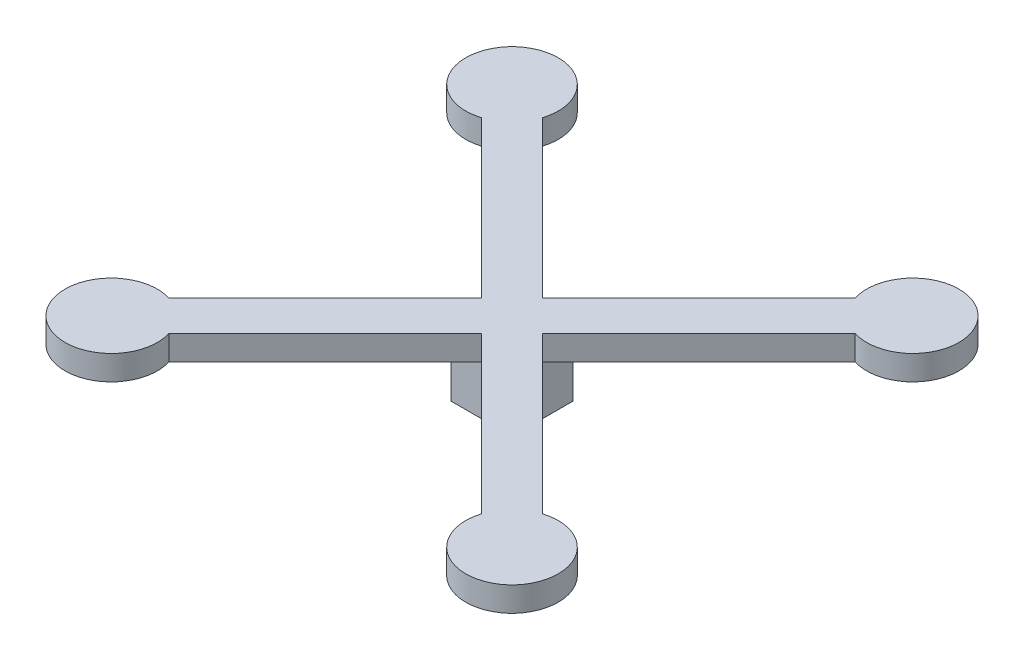
SolidWorks part; units mm, degrees
ref_plane "Front Plane" through (0, 0, 0) normal (0, 0, 1) x (1, 0, 0)
ref_plane "Top Plane" through (0, 0, 0) normal (0, 1, 0) x (1, 0, 0)
ref_plane "Right Plane" through (0, 0, 0) normal (1, 0, 0) x (0, 0, -1)
sketch "Sketch1" plane through (0, 0, 0) normal (0, 1, 0) x (1, 0, 0)
  line L0 (-12.3744, 12.3744) -> (12.3744, -12.3744)
  line L1 (12.3744, -12.3744) -> (175.0089, 150.2602)
  line L2 (175.0089, 150.2602) -> (150.2602, 175.0089)
  line L3 (150.2602, 175.0089) -> (-12.3744, 12.3744)
  line L4 (0, 0) -> (-70.3293, 0) construction
  line L5 (175.0089, -150.2602) -> (12.3744, 12.3744)
  line L6 (12.3744, 12.3744) -> (-12.3744, -12.3744)
  line L7 (-12.3744, -12.3744) -> (150.2602, -175.0089)
  line L8 (150.2602, -175.0089) -> (175.0089, -150.2602)
  line L9 (-150.2602, -175.0089) -> (12.3744, -12.3744)
  line L10 (12.3744, -12.3744) -> (-12.3744, 12.3744)
  line L11 (-12.3744, 12.3744) -> (-175.0089, -150.2602)
  line L12 (-175.0089, -150.2602) -> (-150.2602, -175.0089)
  line L13 (-175.0089, 150.2602) -> (-12.3744, -12.3744)
  line L14 (-12.3744, -12.3744) -> (12.3744, 12.3744)
  line L15 (12.3744, 12.3744) -> (-150.2602, 175.0089)
  line L16 (-150.2602, 175.0089) -> (-175.0089, 150.2602)
  circle A0 centre (162.6346, 162.6346) radius 37.5
  circle A1 centre (162.6346, -162.6346) radius 37.5
  circle A2 centre (-162.6346, -162.6346) radius 37.5
  circle A3 centre (-162.6346, 162.6346) radius 37.5
  point P4 (0, 0)
  point P31 (0, 0)
  dimension "D2" = 35
  dimension "D3" = 75
  dimension "D1" = 230
  dimension "D4" = 45
  dimension "D5" = 4
extrude "Boss-Extrude1" add sketch "Sketch1" along normal blind 20 contours L11 A2 L9 L12 | L9 A2 L11 L12 | A2 L9 L7 L13 L11 | L15 A3 L13 L16 | L13 A3 L15 L16 | A3 L13 L11 L3 L15 | A0 L3 L15 L5 L1 | L3 A0 L1 L2 | L1 A0 L3 L2 | A1 L5 L1 L9 L7 | L5 A1 L7 L8 | L7 A1 L5 L8 | L5 L6 L0 L1 | L7 L9 L0 L6 | L4 L0 L11 | L6 L15 L3 L0 | L6 L4 L13 region at (0, 0, -12.3744) region at (-74.7478, 0, -74.7478) region at (-12.3744, 0, -4.1248) region at (12.3744, 0, 0) region at (-12.3744, 0, 4.1248) region at (0, 0, 12.3744) region at (74.7478, 0, -74.7478) region at (-74.7478, 0, 74.7478) region at (74.7478, 0, 74.7478) region at (167.7502, 0, -167.7502) region at (149.8586, 0, -149.8586) region at (-149.8586, 0, -149.8586) region at (-167.7502, 0, -167.7502) region at (-149.8586, 0, 149.8586) region at (-167.7502, 0, 167.7502) region at (167.7502, 0, 167.7502) region at (149.8586, 0, 149.8586)
sketch "Sketch2" plane through (0, 0, 0) normal (0, -1, 0) x (1, 0, 0)
  line L1 (-24.7487, 24.7487) -> (24.7487, 24.7487)
  line L2 (-24.7487, 24.7487) -> (-24.7487, -24.7487)
  line L3 (-24.7487, -24.7487) -> (24.7487, -24.7487)
  line L4 (24.7487, 24.7487) -> (24.7487, -24.7487)
  line L5 (-24.7487, 24.7487) -> (24.7487, -24.7487) construction
  line L6 (-24.7487, -24.7487) -> (24.7487, 24.7487) construction
  point P0 (0, 0)
extrude "Boss-Extrude2" add sketch "Sketch2" along normal blind 40
